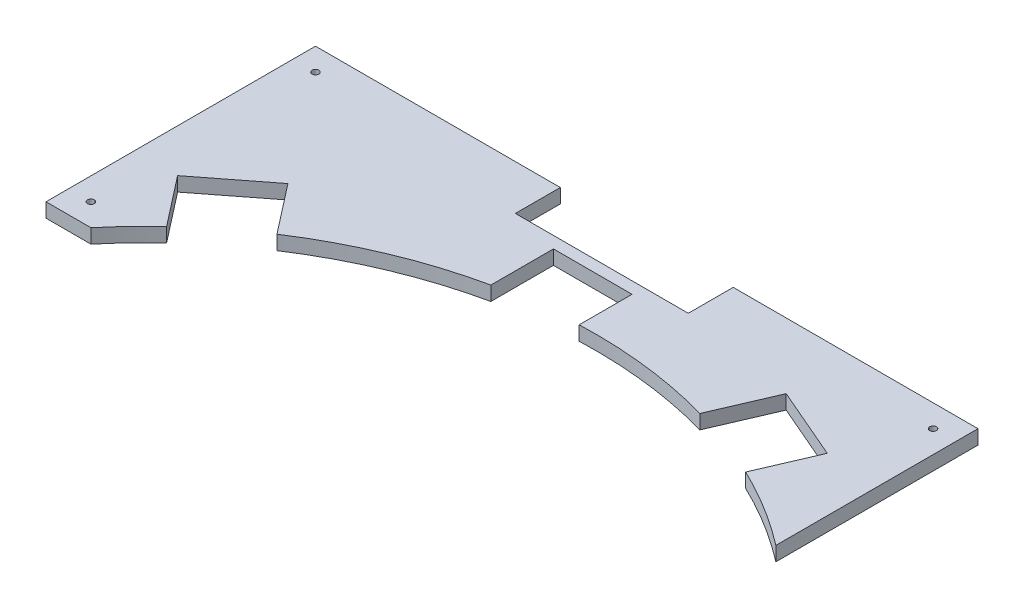
SolidWorks part; units mm, degrees
material "Balsa"
ref_plane "Front Plane" through (0, 0, 0) normal (0, 0, 1) x (1, 0, 0)
ref_plane "Top Plane" through (0, 0, 0) normal (0, 1, 0) x (1, 0, 0)
ref_plane "Right Plane" through (0, 0, 0) normal (1, 0, 0) x (0, 0, -1)
sketch "Sketch1" plane through (0, 0, 0) normal (0, 1, 0) x (1, 0, 0)
  line L0 (-12.3254, 51.9031) -> (-32.3254, 51.9031)
  line L5 (-32.3254, 51.9031) -> (-32.3254, 171.9031)
  line L6 (-32.3254, 171.9031) -> (262.6746, 171.9031)
  line L7 (262.6746, 171.9031) -> (262.6746, 81.9031)
  line L8 (98.8295, 118.8327) -> (98.8295, 146.7001)
  line L9 (98.8295, 146.7001) -> (133.8295, 146.7001)
  line L10 (133.8295, 146.7001) -> (133.8295, 123.1719)
  line L11 (194.8943, 115.852) -> (206.46, 142.6967)
  line L12 (206.46, 142.6967) -> (238.6037, 128.848)
  line L13 (238.6037, 128.848) -> (227.6676, 103.4646)
  line L14 (4.0631, 69.212) -> (-13.1129, 91.2884)
  line L15 (-13.1129, 91.2884) -> (14.5111, 112.7806)
  line L16 (14.5111, 112.7806) -> (31.5953, 90.8222)
  arc A0 (-12.3254, 51.9031) -> (4.0631, 69.212) centre (140.841, -76.7051) cw
  arc A1 (31.5953, 90.8222) -> (98.8295, 118.8327) centre (140.841, -76.7051) cw
  arc A2 (133.8295, 123.1719) -> (194.8943, 115.852) centre (140.841, -76.7051) cw
  arc A3 (227.6676, 103.4646) -> (262.6746, 81.9031) centre (140.841, -76.7051) cw
  circle A4 centre (-22.3254, 161.9031) radius 1.5
  circle A5 centre (252.6746, 161.9031) radius 1.5
  circle A6 centre (-22.3254, 61.9031) radius 1.5
  dimension "D5" = 200
  dimension "D11" = 3
  dimension "D14" = 3
  dimension "D17" = 3
  dimension "D1" = 295
  dimension "D2" = 20
  dimension "D3" = 120
  dimension "D4" = 90
  dimension "D6" = 35
  dimension "D7" = 35
  dimension "D8" = 35
  dimension "D9" = 10
  dimension "D10" = 10
  dimension "D12" = 10
  dimension "D13" = 10
  dimension "D15" = 10
  dimension "D16" = 10
extrude "Boss-Extrude1" add sketch "Sketch1" along normal blind 6.35
sketch "Sketch2" plane through (0, 6.35, 0) normal (0, 1, 0) x (1, 0, 0)
  line L0 (262.6746, 171.9031) -> (-32.3254, 171.9031) construction
  line L1 (76.6746, 171.9031) -> (153.6746, 171.9031)
  line L2 (76.6746, 171.9031) -> (76.6746, 151.9031)
  line L3 (76.6746, 151.9031) -> (153.6746, 151.9031)
  line L4 (153.6746, 171.9031) -> (153.6746, 151.9031)
  line L5 (115.1746, 171.9031) -> (115.1746, 151.9031) construction
  line L6 (115.1746, 171.9031) -> (115.1746, 141.1) construction
  dimension "D1" = 20
  dimension "D2" = 77
extrude "Cut-Extrude1" cut sketch "Sketch2" against normal through all
